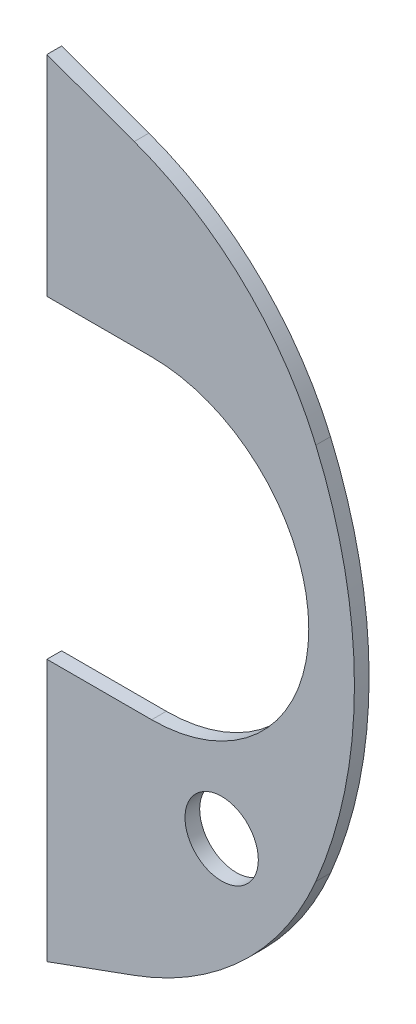
SolidWorks part; units mm, degrees
ref_plane "Front Plane" through (0, 0, 0) normal (0, 0, 1) x (1, 0, 0)
ref_plane "Top Plane" through (0, 0, 0) normal (0, 1, 0) x (1, 0, 0)
ref_plane "Right Plane" through (0, 0, 0) normal (1, 0, 0) x (0, 0, -1)
sketch "Sketch1" plane through (0, 0, 0) normal (0, 0, 1) x (1, 0, 0)
  line L1 (0, 0) -> (5, 0)
  line L2 (0, 0) -> (0, 12.5)
  line L3 (0, 12.5) -> (5, 12.5)
  line L4 (5, 0) -> (5, 12.5) construction
  line L5 (0, 27.5) -> (5, 27.5)
  line L6 (0, 27.5) -> (0, 37.5)
  line L7 (0, 37.5) -> (5, 37.5)
  line L8 (5, 27.5) -> (5, 37.5) construction
  arc A0 (5, 37.5) -> (5, 0) centre (-8.3206, 18.75) cw
  arc A1 (5, 27.5) -> (5, 12.5) centre (5, 20) cw
  dimension "D5" = 23
  dimension "D1" = 12.5
  dimension "D2" = 10
  dimension "D3" = 15
  dimension "D4" = 5
extrude "Boss-Extrude1" add sketch "Sketch1" along normal blind 0.7
sketch "Sketch2" plane through (0, 0, 0.7) normal (0, 0, 1) x (1, 0, 0)
  line L0 (0, 37.5) -> (13.3749, 32.6319)
  line L1 (0, 0) -> (14.6459, 5.3307)
  line L2 (0, 0) -> (5, 0) construction
  line L3 (5, 37.5) -> (0, 37.5) construction
  line L4 (0, 37.5) -> (10.5451, 37.5)
  line L5 (10.5451, 37.5) -> (13.3749, 32.6319)
  line L6 (0, 0) -> (11.6819, 0)
  line L7 (11.6819, 0) -> (14.6459, 5.3307)
  circle A0 centre (8.342, 9.2526) radius 1.75
  point P14 (4.2625, 6.8162)
  point P15 (2.0212, 10.3295)
  point P16 (7.3617, 8.6442)
  point P17 (8.511, 9.4554)
  point P18 (8.342, 9.2526)
  dimension "D3" = 3.5
  dimension "D1" = 20
  dimension "D2" = 20
extrude "Cut-Extrude1" cut sketch "Sketch2" against normal blind 10
fillet "Fillet1" radius 15 2 edges at (8.5426, 34.3907, 0.35) (8.5426, 3.1093, 0.35)
